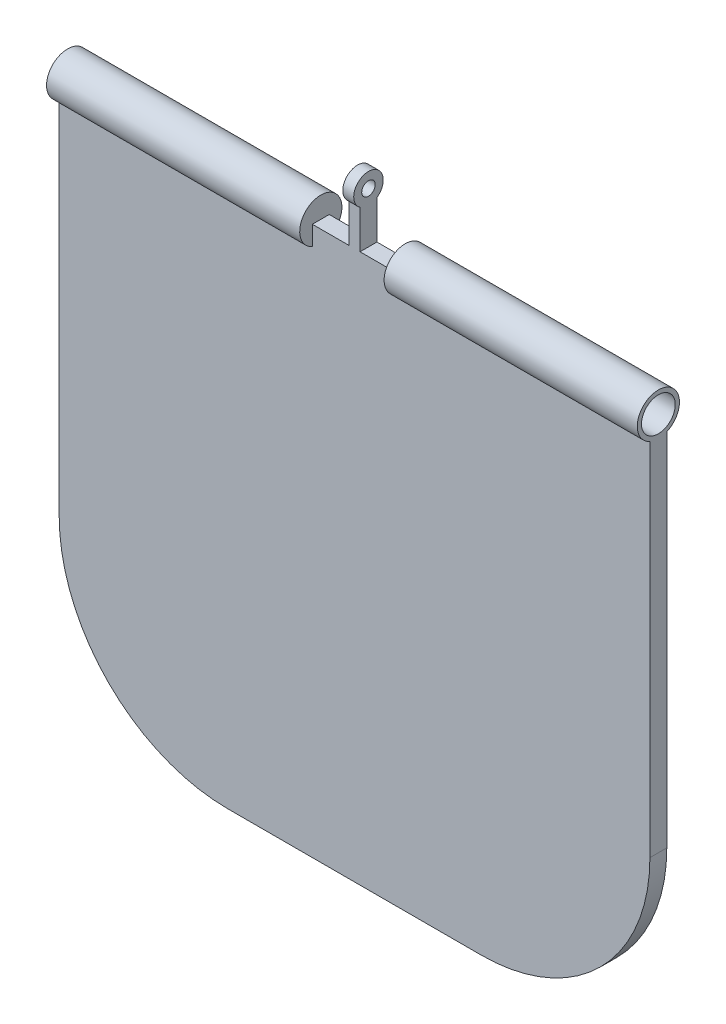
SolidWorks part; units mm, degrees
ref_plane "Front Plane" through (0, 0, 0) normal (0, 0, 1) x (1, 0, 0)
ref_plane "Top Plane" through (0, 0, 0) normal (0, 1, 0) x (1, 0, 0)
ref_plane "Right Plane" through (0, 0, 0) normal (1, 0, 0) x (0, 0, -1)
sketch "Sketch2" plane through (0, 0, 0) normal (0, 0, 1) x (1, 0, 0)
  line L1 (15, -32.5) -> (-15, -32.5)
  line L2 (35, -12.5) -> (35, 32.5)
  line L3 (35, 32.5) -> (-35, 32.5)
  line L4 (-35, -12.5) -> (-35, 32.5)
  line L5 (35, -32.5) -> (-35, 32.5) construction
  line L6 (35, 32.5) -> (-35, -32.5) construction
  arc A0 (15, -32.5) -> (35, -12.5) centre (15, -12.5) ccw
  arc A1 (-15, -32.5) -> (-35, -12.5) centre (-15, -12.5) cw
  point P0 (0, 0)
  dimension "D3" = 20
  dimension "D1" = 65
  dimension "D2" = 70
extrude "Boss-Extrude1" add sketch "Sketch2" along normal blind 2
sketch "Sketch3" plane through (35, 0, 0) normal (1, 0, 0) x (0, 0, -1)
  line L0 (-1, 32.5) -> (-1, 37.5) construction
  line L3 (-2, 32.5) -> (0, 32.5) construction
  circle A0 centre (-1, 32.5) radius 2
  circle A1 centre (-1, 32.5) radius 2.5
  line M4 (0, -12.5) -> (0, 32.5)
  line M5 (0, 32.5) -> (-2, 32.5)
  line M6 (-2, 32.5) -> (-2, -12.5)
  dimension "D2" = 4
  dimension "D3" = 0.5
  dimension "D1" = 5
extrude "Boss-Extrude2" add sketch "Sketch3" against normal blind 30 contours L0 A0 M5 M6 | L0 A0 M5 M4 | A0 M6 M4 M5 | A0 L0 A1 M6 | L0 A0 A1 M4 | A1 A0 M6 M4 region at (35, 32.9195, 2.0066) region at (35, 32.9195, -0.0066) region at (35, 31.5418, 1) region at (35, 33.0316, 2.9841) region at (35, 34.75, 0.946) region at (35, 30.3299, 1)
extrude "Cut-Extrude2" cut sketch "Sketch3<4>" against normal blind 25 contours L0 A0 M5 M6 | A0 M6 M4 M5 | L0 A0 M5 M4 region at (35, 32.9195, 2.0066) region at (35, 32.9195, -0.0066) region at (35, 31.5418, 1)
sketch "Sketch3<4>" plane through (35, 0, 0) normal (1, 0, 0) x (0, 0, -1) same geometry as "Sketch3"
mirror "Mirror1" about plane through (0, 0, 0) normal (1, 0, 0) of "Cut-Extrude2", "Boss-Extrude2"
sketch "Sketch4" plane through (0, 0, 0) normal (1, 0, 0) x (0, 0, -1)
  line L0 (-2, 32.5) -> (-2, 37.0639)
  line L1 (0, 32.5) -> (-2, 32.5) construction
  line L2 (0, 37.0639) -> (0, 32.5)
  line L4 (-1, 32.5) -> (-1, 38.6707) construction
  line L5 (-2, 32.5) -> (0, 32.5)
  circle A0 centre (-1, 38.5) radius 0.8
  circle A1 centre (-1, 38.5) radius 1.75
  dimension "D2" = 1.6
  dimension "D3" = 3.5
  dimension "D1" = 6
extrude "Boss-Extrude3" add sketch "Sketch4" along normal mid plane 1.3 contours L4 L5 L2 A1 | L5 L4 A1 L0 | A1 A0 region at (0, 34.6763, 1.5059) region at (0, 40.0073, 1.7872) region at (0, 34.6763, 0.4941)
